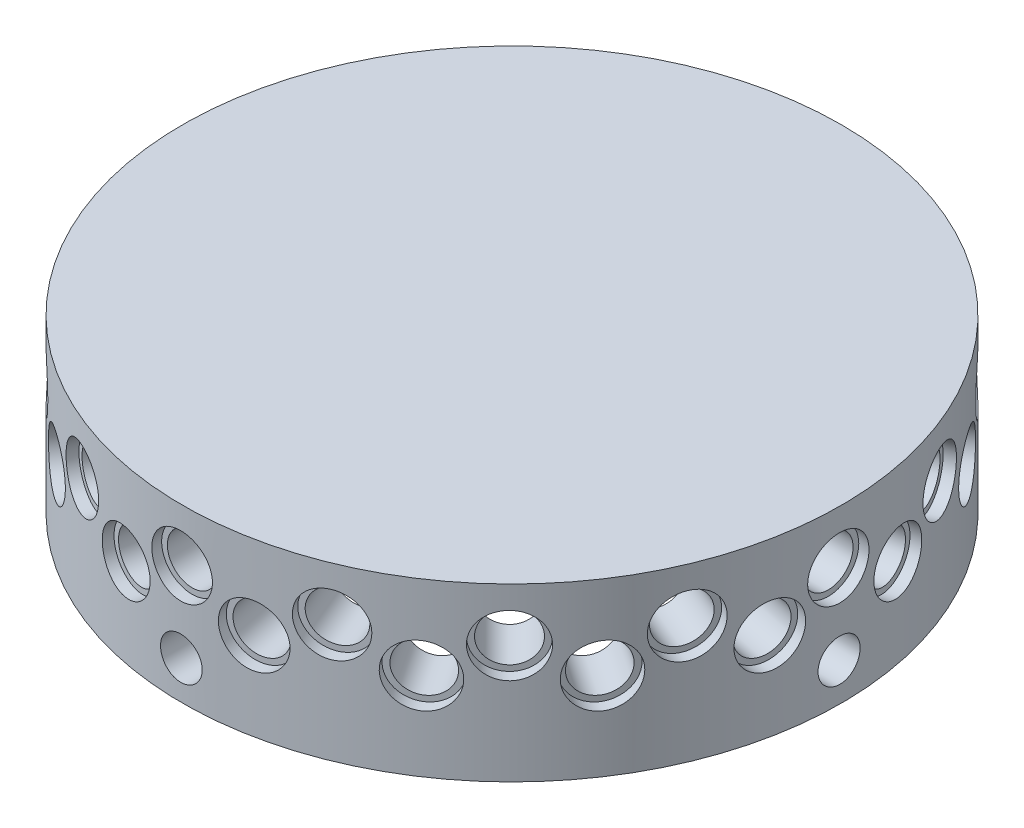
SolidWorks part; units mm, degrees
ref_plane "Płaszczyzna przednia" through (0, 0, 0) normal (0, 0, 1) x (1, 0, 0)
ref_plane "Płaszczyzna górna" through (0, 0, 0) normal (0, 1, 0) x (1, 0, 0)
ref_plane "Płaszczyzna prawa" through (0, 0, 0) normal (1, 0, 0) x (0, 0, -1)
sketch "Szkic1" plane through (0, 0, 0) normal (0, 0, 1) x (1, 0, 0)
  line L0 (0, -200.6294) -> (0, 200.6294) construction
  line L1 (0, 70.8485) -> (-86.5, 70.8485)
  line L2 (-86.5, 70.8485) -> (-86.5, 40.8485)
  line L4 (-86.5, 40.8485) -> (-86.5, 25.8485)
  line L5 (-86.5, 25.8485) -> (-70.5, 25.8485)
  line L6 (-70.5, 25.8485) -> (-70.5, 65.8485)
  line L7 (-70.5, 65.8485) -> (0, 65.8485)
  line L8 (0, 65.8485) -> (0, 70.8485)
  dimension "D1" = 70.5
  dimension "D2" = 40
  dimension "D3" = 5
  dimension "D5" = 16
revolve "Obrót1" add sketch "Szkic1" angle 360 about L0
ref_plane "Płaszczyzna1" through (86.5, 0, 0) normal (1, 0, 0) x (0, 0, -1)
sketch "Szkic2" plane through (86.5, 0, 0) normal (1, 0, 0) x (0, 0, -1)
  line L0 (86.5, 70.8485) -> (-86.5, 70.8485) construction
  circle A0 centre (-0.4671, 56.8485) radius 8
  circle A1 centre (-0.4671, 56.8485) radius 6.5
  dimension "D1" = 14
  dimension "D2" = 16
  dimension "D3" = 13
extrude "Wytnij-wyciągnięcie2" cut sketch "Szkic2" against normal blind 3
sketch "Szkic3" plane through (86.5, 0, 0) normal (1, 0, 0) x (0, 0, -1)
  circle A0 centre (-0.4671, 56.8485) radius 6.5
  circle A1 centre (-0.4671, 56.8485) radius 6.5 construction
extrude "Wytnij-wyciągnięcie3" cut sketch "Szkic3" against normal blind 30
pattern_circular "Szyk kołowy1" count 16 over 360 of "Wytnij-wyciągnięcie2", "Wytnij-wyciągnięcie3"
sketch "Szkic4" plane through (86.5, 0, 0) normal (1, 0, 0) x (0, 0, -1)
  line L0 (-86.5, 25.8485) -> (86.5, 25.8485) construction
  circle A0 centre (-0.4671, 35.8485) radius 5.5
  dimension "D1" = 10
extrude "Wytnij-wyciągnięcie4" cut sketch "Szkic4" against normal blind 30
pattern_circular "Szyk kołowy2" count 4 over 360 about axis through (0, -200.6294, 0) along (0, -1, 0) of "Wytnij-wyciągnięcie4" reverse direction yes
ref_plane "Płaszczyzna2" through (84.8379, 0, 16.8753) normal (0.9808, 0, 0.1951) x (0, -1, 0)
sketch "Szkic8" plane through (84.8379, 0, 16.8753) normal (0.9808, 0, 0.1951) x (0, -1, 0)
  line L0 (-70.8485, 86.5) -> (-70.8485, -86.5) construction
  circle A0 centre (-48.8485, 0) radius 8
  circle A1 centre (-48.8485, 0) radius 6.5
  point P0 (0, 0)
  point P2 (0, 0)
  dimension "D1" = 22
extrude "Wytnij-wyciągnięcie5" cut sketch "Szkic8" against normal blind 3
sketch "Szkic9" plane through (84.8379, 0, 16.8753) normal (0.9808, 0, 0.1951) x (0, -1, 0)
  circle A0 centre (-48.8485, 0) radius 6.5
  circle A2 centre (-48.8485, 0) radius 6.5 construction
  point P2 (0, 0)
extrude "Wytnij-wyciągnięcie6" cut sketch "Szkic9" against normal blind 30
pattern_circular "Szyk kołowy3" count 16 over 360 about axis through (0, -200.6294, 0) along (0, -1, 0) of "Wytnij-wyciągnięcie6", "Wytnij-wyciągnięcie5" reverse direction yes
